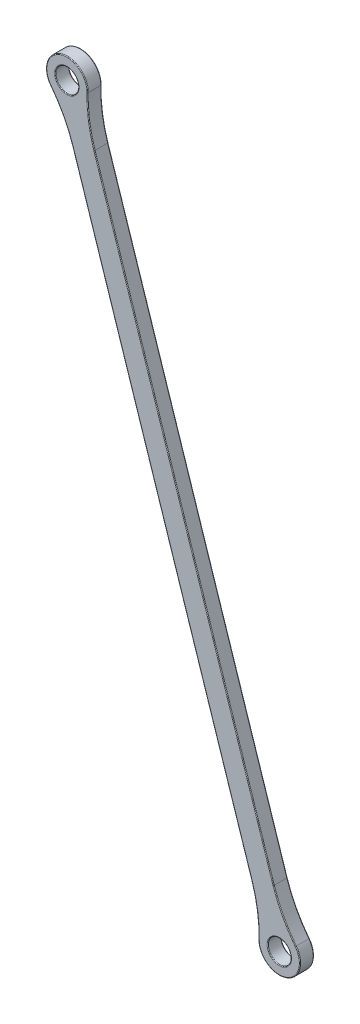
SolidWorks part; units mm, degrees
ref_plane "Front Plane" through (0, 0, 0) normal (0, 0, 1) x (1, 0, 0)
ref_plane "Top Plane" through (0, 0, 0) normal (0, 1, 0) x (1, 0, 0)
ref_plane "Right Plane" through (0, 0, 0) normal (1, 0, 0) x (0, 0, -1)
sketch "Sketch1" plane through (0, 0, 0) normal (0, 0, 1) x (1, 0, 0)
  line L0 (14.5, 81.5) -> (-31.5869, 222.1414) construction
  line L1 (14.5, 81.5) -> (-31.5869, 222.1414) construction
  line L2 (-31.5869, 222.1414) -> (14.5, 81.5) construction
  line L3 (-29.2112, 222.9199) -> (16.8757, 82.2785)
  line L4 (-33.9626, 221.3629) -> (12.1243, 80.7215)
  circle A0 centre (14.5, 81.5) radius 4.5 construction
  circle A1 centre (-31.5869, 222.1414) radius 4.5 construction
  arc A2 (-29.2112, 222.9199) -> (-33.9626, 221.3629) centre (-31.5869, 222.1414) ccw
  arc A3 (12.1243, 80.7215) -> (16.8757, 82.2785) centre (14.5, 81.5) ccw
  arc A4 (-33.9626, 221.3629) -> (-29.2112, 222.9199) centre (-31.5869, 222.1414) ccw
  arc A5 (16.8757, 82.2785) -> (12.1243, 80.7215) centre (14.5, 81.5) ccw
  arc A6 (-32.7975, 217.8072) -> (-28.0461, 219.3642) centre (-31.5869, 222.1414) cw
  arc A7 (10.9592, 84.2771) -> (15.7106, 85.8341) centre (14.5, 81.5) ccw
  point P4 (-8.5435, 151.8207)
  dimension "D1" = 9
  dimension "D2" = 9
  dimension "D3" = 5
extrude "Boss-Extrude1" add sketch "Sketch1" against normal blind 3 contours A6 L4 A2 L3 | A5 L3 A4 L4 | L4 A7 L3 A3 region at (-32.4047, 224.6369, 0) region at (-8.5435, 151.8207, 0) region at (15.862, 77.3436, 0)
fillet "Fillet1" radius 30 4 edges at (-32.7975, 217.8072, -1.5) (-28.0461, 219.3642, -1.5) (10.9592, 84.2771, -1.5) (15.7106, 85.8341, -1.5)
fillet "Fillet2" radius 0.15 20 edges at (-29.0869, 222.1414, -3) (9.6939, 86.7318, -3) (15.9013, 77.2237, -3) (15.2777, 88.5616, -3) (-6.1678, 152.5992, -3) (-26.7808, 216.9096, -3) (-32.9882, 226.4176, -3) (-32.3646, 215.0798, -3) (-10.9192, 151.0422, -3) (17, 81.5, -3) (-29.0869, 222.1414, 0) (-26.7808, 216.9096, 0) (-6.1678, 152.5992, 0) (15.2777, 88.5616, 0) (15.9013, 77.2237, 0) (9.6939, 86.7318, 0) (-10.9192, 151.0422, 0) (-32.3646, 215.0798, 0) (-32.9882, 226.4176, 0) (17, 81.5, 0)
